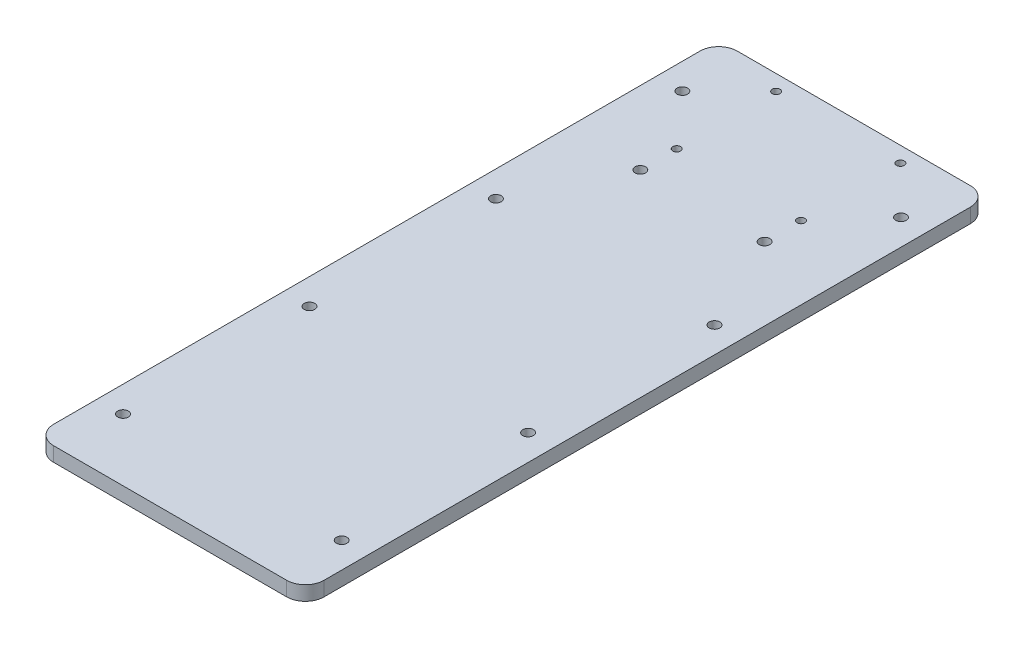
SolidWorks part; units mm, degrees
ref_plane "Front Plane" through (0, 0, 0) normal (0, 0, 1) x (1, 0, 0)
ref_plane "Top Plane" through (0, 0, 0) normal (0, 1, 0) x (1, 0, 0)
ref_plane "Right Plane" through (0, 0, 0) normal (1, 0, 0) x (0, 0, -1)
sketch "Sketch1" plane through (0, 0, 0) normal (0, 1, 0) x (1, 0, 0)
  line L1 (0, 0) -> (95.25, 0)
  line L2 (0, 0) -> (0, -279.4)
  line L3 (0, -279.4) -> (95.25, -279.4)
  line L4 (95.25, 0) -> (95.25, -279.4)
  line L6 (47.625, -6.35) -> (47.625, 0) construction
  line L7 (0, -7.62) -> (0, -271.78) construction
  line L8 (47.625, -279.4) -> (47.625, -81.3177) construction
  line L9 (-7.62, -7.62) -> (-7.62, -271.78)
  line L10 (22.225, -6.35) -> (73.025, -6.35) construction
  line L11 (22.225, -6.35) -> (22.225, -46.99) construction
  line L12 (22.225, -46.99) -> (73.025, -46.99) construction
  line L13 (73.025, -6.35) -> (73.025, -46.99) construction
  line L14 (102.87, -7.62) -> (102.87, -271.78)
  line L15 (2.9464, 0) -> (2.9464, -279.4) construction
  arc A0 (0, 0) -> (-7.62, -7.62) centre (0, -7.62) ccw
  arc A1 (-7.62, -271.78) -> (0, -279.4) centre (0, -271.78) ccw
  arc A2 (102.87, -271.78) -> (95.25, -279.4) centre (95.25, -271.78) cw
  arc A3 (95.25, 0) -> (102.87, -7.62) centre (95.25, -7.62) cw
  circle A4 centre (2.9464, -25.4) radius 2.159
  circle A5 centre (2.9464, -101.6) radius 2.159
  circle A6 centre (22.225, -6.35) radius 1.5875
  circle A7 centre (73.025, -6.35) radius 1.5875
  circle A8 centre (73.025, -46.99) radius 1.5875
  circle A9 centre (22.225, -46.99) radius 1.5875
  circle A10 centre (2.9464, -177.8) radius 2.159
  circle A11 centre (2.9464, -254) radius 2.159
  circle A12 centre (22.225, -61.8602) radius 2.159
  circle A13 centre (73.025, -61.8602) radius 2.159
  circle A14 centre (92.3036, -25.4) radius 2.159
  circle A15 centre (92.3036, -101.6) radius 2.159
  circle A16 centre (92.3036, -254) radius 2.159
  circle A17 centre (92.3036, -177.8) radius 2.159
  point P7 (0, -139.7)
  dimension "D6" = 7.62
  dimension "D7" = 50.8
  dimension "D9" = 3.175
  dimension "D4" = 7.62
  dimension "D10" = 25.4
  dimension "D11" = 4.318
  dimension "D15" = 4.318
  dimension "D1" = 95.25
  dimension "D2" = 279.4
  dimension "D3" = 6.35
  dimension "D5" = 2.9464
  dimension "D8" = 40.64
  dimension "D12" = 101.6
  dimension "D13" = 177.8
  dimension "D14" = 254
  dimension "D16" = 25.4
extrude "Boss-Extrude1" add sketch "Sketch1" along normal blind 5.8928 contours L4 L1 L2 L3 A9 A8 A7 A6 | L9 A1 L2 A0 | A3 L4 A2 L14 region at (47.625, 0, 139.9217) region at (-3.785, 0, 139.7) region at (99.035, 0, 139.7)
